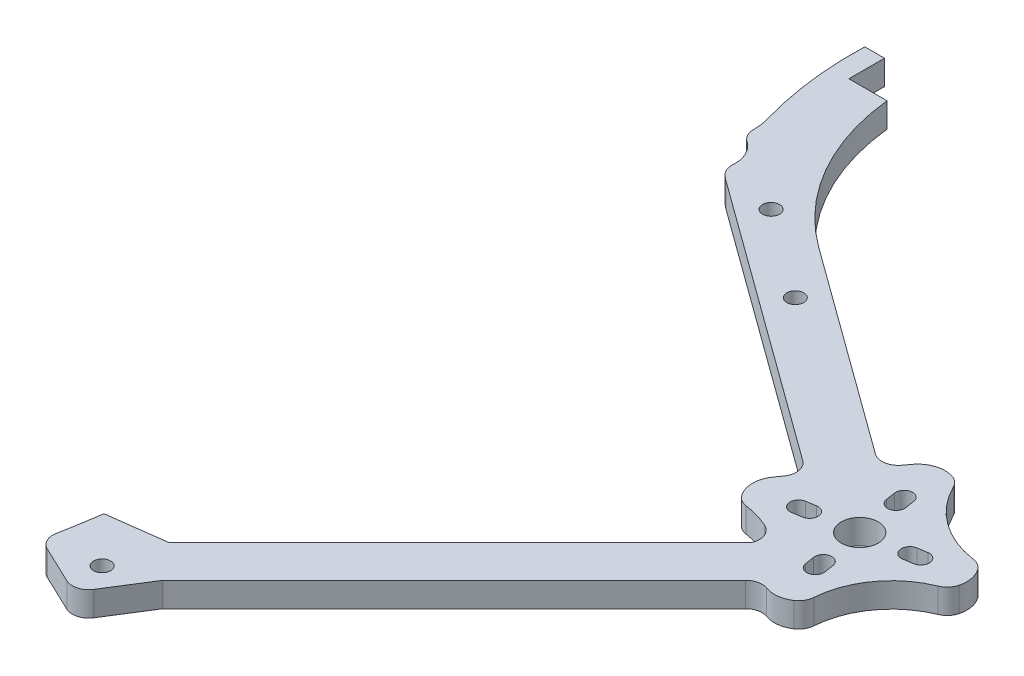
SolidWorks part; units mm, degrees
material "PPS"
ref_plane "前视基准面" through (0, 0, 0) normal (0, 0, 1) x (1, 0, 0)
ref_plane "上视基准面" through (0, 0, 0) normal (0, 1, 0) x (1, 0, 0)
ref_plane "右视基准面" through (0, 0, 0) normal (1, 0, 0) x (0, 0, -1)
sketch "草图3" plane through (0, 0, 0) normal (0, 1, 0) x (1, 0, 0)
  line L0 (0, 0) -> (35.4735, 0) construction
  line L1 (0, 0) -> (62.3757, -45.3186) construction
  line L2 (41.1319, -24.0128) -> (94.6944, -62.9282)
  line L3 (94.6944, -62.9282) -> (100.1314, -55.4448)
  line L4 (100.1314, -55.4448) -> (122.7839, -71.9028)
  line L5 (122.7839, -71.9028) -> (106.3259, -94.5552)
  line L6 (83.6734, -78.0972) -> (106.3259, -94.5552) construction
  line L9 (77.9994, -109.7251) -> (128.6275, -40.0415) construction
  line L11 (103.2286, -75) -> (90.242, -77.0569) construction
  line L13 (111.1302, -73.7485) -> (112.8586, -73.4748) construction
  line L14 (110.8877, -72.2176) -> (112.6161, -71.9438)
  line L15 (111.3726, -75.2794) -> (113.1011, -75.0057)
  line L16 (101.9772, -67.0985) -> (101.7034, -65.37) construction
  line L17 (103.5081, -66.856) -> (103.2343, -65.1276)
  line L18 (100.4463, -67.341) -> (100.1725, -65.6125)
  line L19 (95.3271, -76.2515) -> (93.5987, -76.5252) construction
  line L20 (95.5696, -77.7824) -> (93.8412, -78.0562)
  line L21 (95.0847, -74.7206) -> (93.3562, -74.9943)
  line L22 (104.4801, -82.9015) -> (104.7539, -84.63) construction
  line L23 (102.9492, -83.144) -> (103.223, -84.8724)
  line L24 (106.011, -82.659) -> (106.2848, -84.3875)
  line L36 (68.8077, -72) -> (90.242, -72) construction
  line L51 (41.6712, -139.6547) -> (94.9997, -86.3262)
  line L52 (94.9997, -86.3262) -> (83.6734, -78.0972)
  line L58 (47.1809, -146.1658) -> (101.962, -91.3847)
  line L61 (101.962, -91.3847) -> (106.3259, -94.5552)
  line L63 (31.6811, -151.7709) -> (40.8875, -156.1591)
  line L64 (47.1809, -146.1658) -> (40.8875, -156.1591)
  line L65 (41.6712, -139.6547) -> (31.2614, -141.0241)
  line L66 (42.309, -153.902) -> (47.6512, -145.4189) construction
  line L67 (31.6811, -151.7709) -> (38.4796, -155.0114) construction
  line L68 (89.1104, -70.6138) -> (83.6734, -78.0972)
  line L69 (35.5479, -31.6984) -> (89.1104, -70.6138)
  circle A5 centre (103.2286, -75) radius 3.375
  arc A6 (110.8877, -72.2176) -> (111.3726, -75.2794) centre (111.1302, -73.7485) ccw
  arc A7 (113.1011, -75.0057) -> (112.6161, -71.9438) centre (112.8586, -73.4748) ccw
  arc A8 (103.5081, -66.856) -> (100.4463, -67.341) centre (101.9772, -67.0985) cw
  arc A9 (100.1725, -65.6125) -> (103.2343, -65.1276) centre (101.7034, -65.37) cw
  arc A10 (95.5696, -77.7824) -> (95.0847, -74.7206) centre (95.3271, -76.2515) ccw
  arc A11 (93.3562, -74.9943) -> (93.8412, -78.0562) centre (93.5987, -76.5252) ccw
  arc A12 (102.9492, -83.144) -> (106.011, -82.659) centre (104.4801, -82.9015) cw
  arc A13 (106.2848, -84.3875) -> (103.223, -84.8724) centre (104.7539, -84.63) cw
  arc A16 (41.1319, -24.0128) -> (35.5479, -31.6984) centre (38.3399, -27.8556) ccw
  circle A17 centre (103.2286, -75) radius 66.25 construction
  circle A18 centre (44.0442, -32) radius 1.55
  circle A19 centre (60.2246, -43.7557) radius 1.55
  circle A28 centre (39.335, -149.4323) radius 1.55
  arc A29 (30.0249, -148.5011) -> (31.2329, -97.7907) centre (-122.0773, -119.5082) ccw construction
  arc A33 (31.2614, -141.0241) -> (30.0249, -148.5011) centre (-122.0773, -119.5082) cw
  arc A34 (30.0249, -148.5011) -> (31.6811, -151.7709) centre (32.9719, -149.0628) ccw construction
  arc A35 (30.0249, -148.5011) -> (31.6811, -151.7709) centre (32.9719, -149.0628) ccw
  point P11 (114.5549, -83.229)
  point P20 (111.9944, -73.6116)
  point P27 (101.8403, -66.2343)
  point P35 (94.4629, -76.3884)
  point P42 (104.617, -83.7657)
  point P54 (94.9997, -86.3262)
  dimension "D2" = 45
  dimension "D3" = 6.75
  dimension "D4" = 1.55
  dimension "D7" = 14
  dimension "D11" = 132.5
  dimension "D12" = 3.1
  dimension "D26" = 8.5
  dimension "D27" = 3.1
  dimension "D1" = 36
  dimension "D5" = 1.75
  dimension "D6" = 8
  dimension "D8" = 14
  dimension "D9" = 4.75
  dimension "D10" = 75
  dimension "D13" = 32
  dimension "D14" = 20
  dimension "D22" = 72
  dimension "D25" = 45
extrude "凸台-拉伸1" add sketch "草图3" along normal blind 4.5 contours L5 L4 L3 L2 A16 L69 L52 L51 A19 A18 A11 L21 A10 L20 A7 L15 A6 L14 region at (66.9596, 0, 44.7829)
fillet "圆角-美观1" radius 5 4 edges at (100.1314, 2.25, 55.4448) (122.7839, 2.25, 71.9028) (106.3259, 2.25, 94.5552) (83.6734, 2.25, 78.0972)
sketch "草图4" plane through (0, 4.5, 0) normal (0, 1, 0) x (1, 0, 0)
  line L0 (104.1765, -58.3837) -> (118.7388, -68.9638)
  line L1 (119.8449, -75.9478) -> (109.2648, -90.5101)
  line L3 (103.2286, -75) -> (124.6569, -90.5685) construction
  line L4 (103.2286, -75) -> (89.033, -94.5387) construction
  line L5 (87.7185, -81.0362) -> (102.2808, -91.6163)
  line L6 (96.4624, -84.313) -> (94.9997, -86.3262)
  line L7 (41.1319, -24.0128) -> (94.6944, -62.9282) construction
  arc A2 (102.2808, -91.6163) -> (87.7185, -81.0362) centre (86.1651, -98.4859) ccw
  arc A8 (118.7388, -68.9638) -> (104.1765, -58.3837) centre (120.2922, -51.5141) cw
  arc A9 (119.8449, -75.9478) -> (109.2648, -90.5101) centre (124.6569, -90.5685) ccw
  line M97 (87.7185, -81.0362) -> (94.9997, -86.3262)
extrude "圆弧-美观2" cut sketch "草图4" against normal up to next contours A8 L0 | L1 A9 | L6 A2 M97 region at (110.8688, 4.5, 64.4842) region at (113.6066, 4.5, 82.54) region at (92.8302, 4.5, 83.5118)
fillet "圆角-美观3" radius 3 10 edges at (104.1765, 2.25, 58.3837) (118.7388, 2.25, 68.9638) (119.8449, 2.25, 75.9478) (94.6944, 2.25, 62.9282) (40.8875, 2.25, 156.1591) (109.2648, 2.25, 90.5101) (101.962, 2.25, 91.3847) (89.1104, 2.25, 70.6138) (87.7185, 2.25, 81.0362) (96.4624, 2.25, 84.313)
sketch "草图5" plane through (0, 0, 0) normal (0, 1, 0) x (1, 0, 0)
  line L0 (0, 0) -> (132.1913, 0) construction
  line L1 (0, 0) -> (0, 63.0505) construction
  line L2 (41.1319, -24.0128) -> (54.395, -33.649)
  line L3 (30.5, 2.25) -> (26.9026, 2.25)
  line L4 (30.5, 2.25) -> (30.5, -3.25)
  line L5 (30.5, -3.25) -> (30.5, -4.25)
  line L6 (30.5, -4.25) -> (37.4677, -4.25)
  line L7 (41.1319, -24.0128) -> (92.2673, -61.1648) construction
  line L8 (37.3772, -3.25) -> (30.5, -3.25) construction
  line L9 (30.5, -3.25) -> (30.5, 3.25) construction
  line L10 (30.5, 3.25) -> (26.9448, 3.25) construction
  line L11 (41.1319, -24.0128) -> (35.5479, -31.6984)
  line L13 (34.4971, -25.0636) -> (29.8517, -19.5014) construction
  arc A0 (34.4971, -25.0636) -> (41.1319, -24.0128) centre (38.3399, -27.8556) cw construction
  arc A1 (34.4971, -25.0636) -> (35.5479, -31.6984) centre (38.3399, -27.8556) ccw construction
  arc A2 (29.8211, -20.7007) -> (35.5479, -31.6984) centre (43.7171, -20.4546) ccw
  arc A3 (29.8211, -20.7007) -> (29.4289, -18.099) centre (19.8227, -20.8778) ccw
  arc A6 (26.9026, 2.25) -> (29.4289, -18.099) centre (91.9966, 0) ccw
  arc A7 (29.8202, 19.4008) -> (29.8202, -19.4008) centre (91.9966, 0) ccw construction
  arc A8 (54.395, -33.649) -> (37.3772, -3.25) centre (78.8424, 0) cw construction
  arc A9 (29.4289, -18.099) -> (26.9448, 3.25) centre (91.9966, 0) cw construction
  arc A12 (41.1319, -24.0128) -> (35.5479, -31.6984) centre (38.3399, -27.8556) ccw construction
  arc A14 (54.395, 33.649) -> (54.395, -33.649) centre (78.8424, 0) ccw construction
  arc A15 (37.4677, -4.25) -> (42.5499, -20.3171) centre (78.8424, 0) ccw
  arc A16 (54.395, -33.649) -> (42.5499, -20.3171) centre (78.8424, 0) cw
  dimension "D1" = 3.25
  dimension "D5" = 1
  dimension "D2" = 3.25
  dimension "D3" = 30.5
  dimension "D4" = 1
extrude "机臂配合防旋转" add sketch "草图5" along normal up to surface (4.5 mm away) up to face at (39.335, 4.5, 150.9823)
sketch "草图7" plane through (0, 0, 0) normal (0, 1, 0) x (1, 0, 0)
  circle A1 centre (44.0442, -32) radius 1.55 construction
  circle A6 centre (28, -28) radius 3.15 construction
  circle A7 centre (28, -28) radius 5.5
  point P5 (0, 0)
  point P7 (44.0201, -30.4502)
  dimension "D1" = 11
  dimension "D2" = 1.55
  dimension "D3" = 4
extrude "减震球让位" cut sketch "草图7" along normal through all
fillet "圆角1" radius 3 2 edges at (33.2595, 2.25, 29.6087) (30.034, 2.25, 22.8899)
